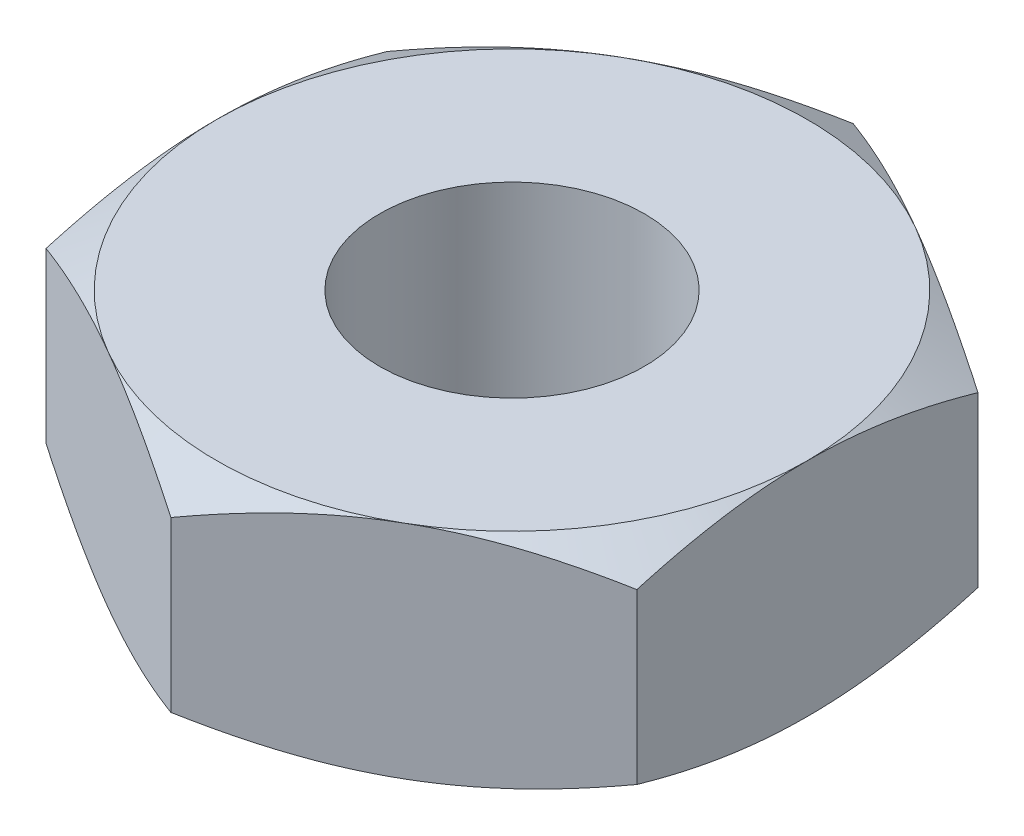
SolidWorks part; units mm, degrees
material "6061-T6 (SS)"
ref_plane "Front Plane" through (0, 0, 0) normal (0, 0, 1) x (1, 0, 0)
ref_plane "Top Plane" through (0, 0, 0) normal (0, 1, 0) x (1, 0, 0)
ref_plane "Right Plane" through (0, 0, 0) normal (1, 0, 0) x (0, 0, -1)
sketch "Sketch7" plane through (0, 0, 0) normal (0, 1, 0) x (1, 0, 0)
  line L0 (-3.175, 0) -> (3.175, 0) construction
  line L1 (-1.4224, 0) -> (1.4224, 0) construction
  line L2 (-3.175, 0) -> (-3.175, -0.635) construction
  point P4 (0, 0)
  point P8 (0, 0)
sketch "Sketch6" plane through (0, 0, 0) normal (1, 0, 0) x (0, 0, -1)
  line L0 (0, 1.1906) -> (0, -1.1906) construction
  point P4 (0, 0)
sketch "Sketch1" plane through (0, 0, 0) normal (0, 1, 0) x (1, 0, 0)
  line L1 (-3.175, 1.8331) -> (-3.175, -1.8331)
  line L2 (-3.175, -1.8331) -> (0, -3.6662)
  line L3 (0, -3.6662) -> (3.175, -1.8331)
  line L4 (3.175, -1.8331) -> (3.175, 1.8331)
  line L5 (3.175, 1.8331) -> (0, 3.6662)
  line L6 (0, 3.6662) -> (-3.175, 1.8331)
  circle A0 centre (0, 0) radius 3.175 construction
  circle A1 centre (0, 0) radius 1.4224
extrude "Boss-Extrude1" add sketch "Sketch1" along normal mid plane 2.3813
sketch "Sketch5" plane through (0, 1.1906, 0) normal (0, 1, 0) x (1, 0, 0)
  circle A0 centre (0, 0) radius 3.175 construction
  circle A1 centre (0, 0) radius 3.175
extrude "Cut-Extrude2" cut sketch "Sketch5" against normal through all draft 60 flip side to cut
mirror "Mirror1" about plane through (0, 0, 0) normal (0, 1, 0) of "Cut-Extrude2"
sketch "Sketch14" plane through (0, 1.1906, 0) normal (0, 1, 0) x (1, 0, 0)
  line L0 (-1.4224, 0) -> (1.4224, 0) construction
  line L1 (0, 1.4224) -> (0, -1.4224) construction
  circle A0 centre (0, 0) radius 1.4224 construction
  point P7 (0, 0)
  point P11 (0, 0)
  point P12 (0, -1.4224)
  point P13 (-1.4224, 0)
  point P14 (0, 1.4224)
  point P15 (1.4224, 0)
sketch "Sketch8" [suppressed] plane through (0, 1.1906, 0) normal (0, 1, 0) x (1, 0, 0)
  circle A0 centre (0, 0) radius 1.4224 construction
  circle A1 centre (0, 0) radius 1.4224
extrude "Boss-Extrude2" [suppressed] add sketch "Sketch8" against normal up to surface (2.3812 mm away) separate body
sketch "Sketch9" [suppressed] plane through (0, 1.1906, 0) normal (0, 1, 0) x (1, 0, 0)
  circle A0 centre (0, 0) radius 1.4224 construction
  circle A1 centre (0, 0) radius 1.4224
extrude "Boss-Extrude3" [suppressed] add sketch "Sketch9" against normal up to surface (2.3812 mm away)
sketch "Sketch10" [suppressed] plane through (0, 1.1906, 0) normal (0, 1, 0) x (1, 0, 0)
  circle A0 centre (0, 0) radius 1.4224 construction
  circle A1 centre (0, 0) radius 1.4224
curve "Helix/Spiral1" [suppressed] pitch 0.635 height 3.0162 turns 4.75
sketch "Sketch11" [suppressed] plane through (0, 0, 0) normal (1, 0, 0) x (0, 0, -1)
  line L0 (-1.4224, 1.1906) -> (-1.4224, 1.7462)
  line L1 (1.4224, 1.1906) -> (-1.4224, 1.1906) construction
  line L2 (-1.4224, 1.7462) -> (-1.01, 1.5081)
  line L3 (-1.01, 1.5081) -> (-1.01, 1.4287)
  line L4 (-1.01, 1.4287) -> (-1.4224, 1.1906)
  line L5 (-1.4224, 1.4684) -> (-1.01, 1.4684) construction
  line L6 (-1.2162, 1.6272) -> (-1.2162, 1.3097) construction
  spline S0 degree 3 poles (-1.4224, 1.1906) (-1.4224, 1.1773) (-1.3463, 1.1504) (-1.0218, 1.1102) (-0.5376, 1.07) (0.0306, 1.0298) (0.594, 0.9895) (1.0646, 0.9493) (1.3688, 0.9091) (1.4592, 0.8689) (1.3214, 0.8287) (0.9772, 0.7885) (0.4803, 0.7482) (-0.0917, 0.708) (-0.6494, 0.6678) (-1.1055, 0.6276) (-1.389, 0.5874) (-1.4553, 0.5472) (-1.2942, 0.5069) (-0.9309, 0.4667) (-0.4221, 0.4265) (0.1527, 0.3863) (0.7036, 0.3461) (1.1445, 0.3059) (1.4066, 0.2656) (1.4489, 0.2254) (1.2648, 0.1852) (0.883, 0.145) (0.3632, 0.1048) (-0.2133, 0.0646) (-0.7565, 0.0243) (-1.1815, -0.0159) (-1.4219, -0.0561) (-1.44, -0.0963) (-1.2331, -0.1365) (-0.8335, -0.1767) (-0.3036, -0.217) (0.2737, -0.2572) (0.8082, -0.2974) (1.2164, -0.3376) (1.4346, -0.3778) (1.4285, -0.418) (1.1992, -0.4583) (0.7825, -0.4985) (0.2436, -0.5387) (-0.3335, -0.5789) (-0.8584, -0.6191) (-1.2492, -0.6593) (-1.4448, -0.6996) (-1.4146, -0.7398) (-1.1633, -0.78) (-0.7302, -0.8202) (-0.183, -0.8604) (0.3927, -0.9006) (0.9071, -0.9409) (1.2798, -0.9811) (1.4524, -1.0213) (1.3981, -1.0615) (1.1253, -1.1017) (0.6766, -1.1419) (0.1222, -1.1822) (-0.4513, -1.2224) (-0.9543, -1.2626) (-1.3081, -1.3028) (-1.4576, -1.343) (-1.3792, -1.3832) (-1.0853, -1.4235) (-0.6218, -1.4637) (-0.0612, -1.5039) (0.5091, -1.5441) (0.9997, -1.5843) (1.3342, -1.6245) (1.4601, -1.6648) (1.3579, -1.705) (1.0433, -1.7452) (0.5665, -1.7854) (0.1874, -1.8123) (0, -1.8256) knots 0 0 0 0 0.013333 0.026667 0.04 0.053333 0.066667 0.08 0.093333 0.106667 0.12 0.133333 0.146667 0.16 0.173333 0.186667 0.2 0.213333 0.226667 0.24 0.253333 0.266667 0.28 0.293333 0.306667 0.32 0.333333 0.346667 0.36 0.373333 0.386667 0.4 0.413333 0.426667 0.44 0.453333 0.466667 0.48 0.493333 0.506667 0.52 0.533333 0.546667 0.56 0.573333 0.586667 0.6 0.613333 0.626667 0.64 0.653333 0.666667 0.68 0.693333 0.706667 0.72 0.733333 0.746667 0.76 0.773333 0.786667 0.8 0.813333 0.826667 0.84 0.853333 0.866667 0.88 0.893333 0.906667 0.92 0.933333 0.946667 0.96 0.973333 0.986667 1 1 1 1 construction
  dimension "D1" = 60
  dimension "D2" = 0.0794
  dimension "D3" = 0.3175
sweep "Cut-Sweep1" [suppressed] cut profiles "Sketch11" path "Helix/Spiral1"
combine bodies "Combine1" [suppressed] operation type subtract main body 107 bodies to subtract 108
sketch "Sketch12" [suppressed] plane through (0, 1.1906, 0) normal (0, 1, 0) x (1, 0, 0)
  circle A1 centre (0, 0) radius 1.4224
  circle A2 centre (0, 0) radius 1.4224
  dimension "D1" = 0
extrude "Cut-Extrude3" [suppressed] cut sketch "Sketch12" against normal through all draft 45
sketch "Sketch13" [suppressed] plane through (0, -1.1906, 0) normal (0, -1, 0) x (1, 0, 0)
  circle A1 centre (0, 0) radius 1.4224
  circle A2 centre (0, 0) radius 1.4224
  dimension "D1" = 0
extrude "Cut-Extrude4" [suppressed] cut sketch "Sketch13" against normal through all draft 45
equation "\"D3@Helix/Spiral1\"=\"Thickness@Sketch6\"+\"Pitch@Sketch7\""
equation "\"Height@Boss-Extrude1\"=\"Thickness@Sketch6\""
equation "\"D4@Helix/Spiral1\"=\"Pitch@Sketch7\""
equation "\"D2@Sketch11\"=\"Pitch@Sketch7\"*.125"
equation "\"D3@Sketch11\"=\"Pitch@Sketch7\"*.5"
